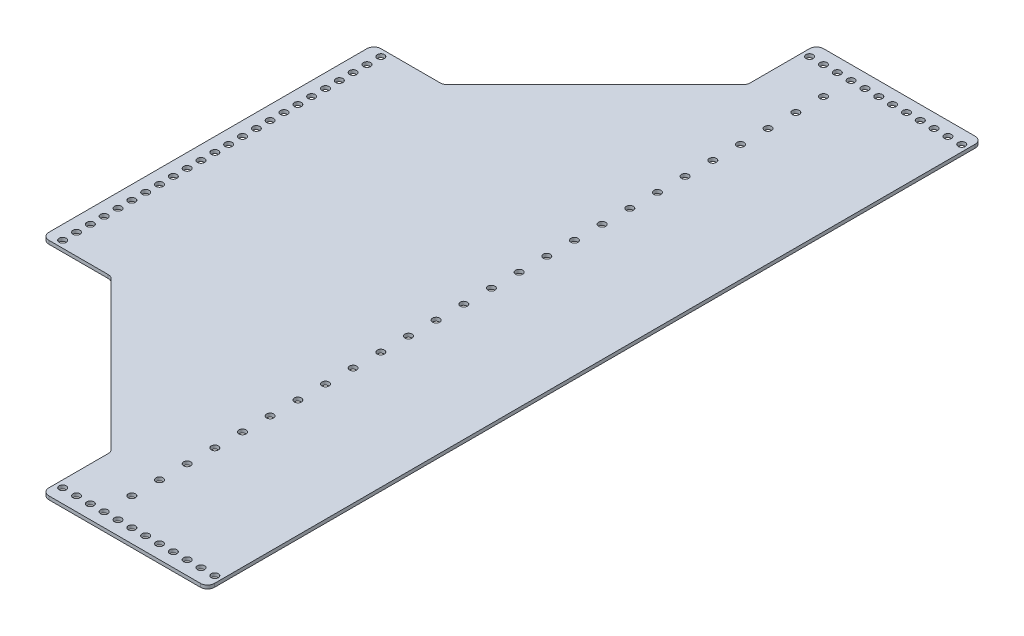
SolidWorks part; units mm, degrees
material "PC High Viscosity"
ref_plane "Front Plane" through (0, 0, 0) normal (0, 0, 1) x (1, 0, 0)
ref_plane "Top Plane" through (0, 0, 0) normal (0, 1, 0) x (1, 0, 0)
ref_plane "Right Plane" through (0, 0, 0) normal (1, 0, 0) x (0, 0, -1)
sketch "Sketch1" plane through (0, 0, 0) normal (0, 1, 0) x (1, 0, 0)
  line L0 (0, 203.2) -> (63.5, 203.2)
  line L1 (203.2, 0) -> (508, 0) construction
  line L2 (0, 203.2) -> (0, 508)
  line L3 (203.2, 711.2) -> (355.2031, 711.2)
  line L4 (711.2, 203.2) -> (711.2, 508) construction
  line L5 (63.5, 203.2) -> (133.097, 133.603)
  line L6 (203.2, 63.5) -> (203.2, 0) construction
  line L7 (0, 508) -> (63.5, 508)
  line L8 (63.5, 508) -> (203.2, 647.7)
  line L9 (203.2, 647.7) -> (203.2, 711.2)
  line L10 (508, 711.2) -> (508, 647.7) construction
  line L11 (508, 647.7) -> (577.597, 578.103) construction
  line L12 (647.7, 508) -> (711.2, 508) construction
  line L13 (508, 0) -> (508, 63.5) construction
  line L14 (508, 63.5) -> (647.7, 203.2) construction
  line L15 (647.7, 203.2) -> (711.2, 203.2) construction
  line L16 (0, 0) -> (203.2, 0) construction
  line L17 (0, 0) -> (0, 203.2) construction
  line L18 (508, 0) -> (711.2, 0) construction
  line L19 (711.2, 0) -> (711.2, 203.2) construction
  line L20 (508, 711.2) -> (711.2, 711.2) construction
  line L21 (711.2, 508) -> (711.2, 711.2) construction
  line L22 (0, 508) -> (0, 711.2) construction
  line L23 (0, 711.2) -> (203.2, 711.2) construction
  line L25 (133.097, 133.603) -> (203.2, 63.5) construction
  line L26 (577.597, 578.103) -> (647.7, 508) construction
  line L27 (355.2031, 711.2) -> (355.2031, 0)
  line L28 (355.2031, 0) -> (203.2, 0)
  line L29 (203.2, 0) -> (203.2, 63.5)
  line L30 (203.2, 63.5) -> (133.097, 133.603)
  line L31 (355.2031, 711.2) -> (508, 711.2) construction
  dimension "D1" = 711.2
  dimension "D2" = 63.5
  dimension "D3" = 45
  dimension "D4" = 203.2
  dimension "D5" = 98.425
  dimension "D6" = 152.7969
extrude "Boss-Extrude2" add sketch "Sketch1" along normal mid plane 3.175
sketch "Sketch2" plane through (0, 1.5875, 0) normal (0, 1, 0) x (1, 0, 0)
  line L0 (355.2031, 711.2) -> (203.2, 711.2) construction
  line L1 (203.2, 711.2) -> (203.2, 647.7) construction
  line L2 (63.5, 508) -> (0, 508) construction
  line L3 (0, 508) -> (0, 203.2) construction
  line L4 (203.2, 0) -> (355.2031, 0) construction
  circle A0 centre (209.55, 698.5) radius 3.2639
  circle A1 centre (12.7, 501.65) radius 3.2639
  circle A2 centre (209.55, 12.7) radius 3.2639
  dimension "D3" = 6.5278
  dimension "D1" = 12.7
  dimension "D2" = 6.35
  dimension "D4" = 6.35
  dimension "D5" = 12.7
  dimension "D6" = 12.7
extrude "Cut-Extrude1" cut sketch "Sketch2" against normal through all
fillet "Fillet1" radius 6.35 10 edges at (0, 0, -508) (63.5, 0, -508) (203.2, 0, -647.7) (63.5, 0, -203.2) (0, 0, -203.2) (203.2, 0, -711.2) (355.2031, 0, -711.2) (355.2031, 0, 0) (203.2, 0, 0) (203.2, 0, -63.5)
pattern_linear "LPattern1" count 24 spacing 12.7 along (0, 0, 1) of face at (12.7, -1.5875, -498.3861)
pattern_linear "LPattern2" count 12 spacing 12.7 along (1, 0, 0) of face at (209.55, -1.5875, -695.2361) of face at (209.55, -1.5875, -9.4361)
sketch "Sketch3" plane through (0, 1.5875, 0) normal (0, 1, 0) x (1, 0, 0)
  line L0 (247.65, 711.2) -> (247.65, 0) construction
  line L1 (348.8531, 711.2) -> (209.55, 711.2) construction
  line L2 (209.55, 0) -> (348.8531, 0) construction
  line L3 (0, 501.65) -> (0, 209.55) construction
  circle A0 centre (247.65, 698.5) radius 3.2639 construction
  circle A1 centre (247.65, 698.5) radius 3.2639
  circle A2 centre (247.65, 673.1) radius 3.2639
  circle A3 centre (247.65, 647.7) radius 3.2639
  circle A4 centre (247.65, 622.3) radius 3.2639
  circle A5 centre (247.65, 596.9) radius 3.2639
  circle A6 centre (247.65, 571.5) radius 3.2639
  circle A7 centre (247.65, 546.1) radius 3.2639
  circle A8 centre (247.65, 520.7) radius 3.2639
  circle A9 centre (247.65, 495.3) radius 3.2639
  circle A10 centre (247.65, 469.9) radius 3.2639
  circle A11 centre (247.65, 444.5) radius 3.2639
  circle A12 centre (247.65, 419.1) radius 3.2639
  circle A13 centre (247.65, 393.7) radius 3.2639
  circle A14 centre (247.65, 368.3) radius 3.2639
  circle A15 centre (247.65, 342.9) radius 3.2639
  circle A16 centre (247.65, 317.5) radius 3.2639
  circle A17 centre (247.65, 292.1) radius 3.2639
  circle A18 centre (247.65, 266.7) radius 3.2639
  circle A19 centre (247.65, 241.3) radius 3.2639
  circle A20 centre (247.65, 215.9) radius 3.2639
  circle A21 centre (247.65, 190.5) radius 3.2639
  circle A22 centre (247.65, 165.1) radius 3.2639
  circle A23 centre (247.65, 139.7) radius 3.2639
  circle A24 centre (247.65, 114.3) radius 3.2639
  circle A25 centre (247.65, 88.9) radius 3.2639
  circle A26 centre (247.65, 63.5) radius 3.2639
  circle A27 centre (247.65, 38.1) radius 3.2639
  dimension "D1" = 247.65
  dimension "D3" = 25.4
  dimension "D2" = 27
extrude "Cut-Extrude2" cut sketch "Sketch3" against normal through all
